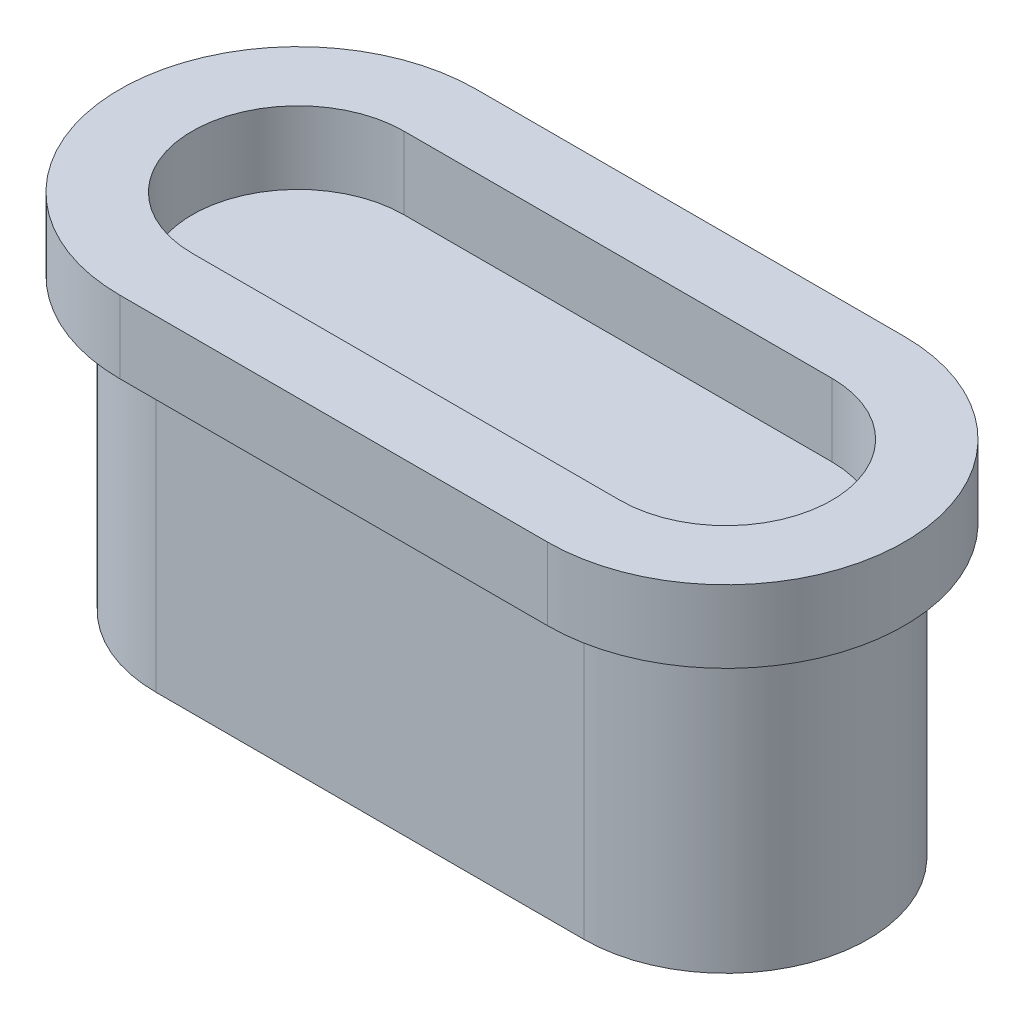
SolidWorks part; units mm, degrees
ref_plane "前视基准面" through (0, 0, 0) normal (0, 0, 1) x (1, 0, 0)
ref_plane "上视基准面" through (0, 0, 0) normal (0, 1, 0) x (1, 0, 0)
ref_plane "右视基准面" through (0, 0, 0) normal (1, 0, 0) x (0, 0, -1)
other "Configuration Table"
sketch "草图1" plane through (0, 0, 0) normal (0, 1, 0) x (1, 0, 0)
  line L0 (0, 0) -> (59.0926, 0) construction
  line L1 (0, 19.6126) -> (59.0926, 19.6126)
  line L2 (0, -19.6126) -> (59.0926, -19.6126)
  arc A0 (0, 19.6126) -> (0, -19.6126) centre (0, 0) ccw
  arc A1 (59.0926, -19.6126) -> (59.0926, 19.6126) centre (59.0926, 0) ccw
  point P3 (29.5463, 0)
extrude "凸台-拉伸1" add sketch "草图1" along normal blind 20 and the other way blind 20
sketch "草图4" plane through (0, 20, 0) normal (0, 1, 0) x (1, 0, 0)
  line L2 (0, -19.6126) -> (59.0926, -19.6126)
  line L3 (59.0926, 19.6126) -> (0, 19.6126)
  line L4 (0, -19.6126) -> (59.0926, -19.6126)
  line L5 (59.0926, 19.6126) -> (0, 19.6126)
  arc A2 (0, 19.6126) -> (0, -19.6126) centre (0, 0) ccw
  arc A3 (59.0926, -19.6126) -> (59.0926, 19.6126) centre (59.0926, 0) ccw
  arc A4 (0, 19.6126) -> (0, -19.6126) centre (0, 0) ccw
  arc A5 (59.0926, -19.6126) -> (59.0926, 19.6126) centre (59.0926, 0) ccw
  dimension "D1" = 0
extrude "拉伸-薄壁1" add sketch "草图4" along normal blind 10 thin thin type mid plane wall 10
